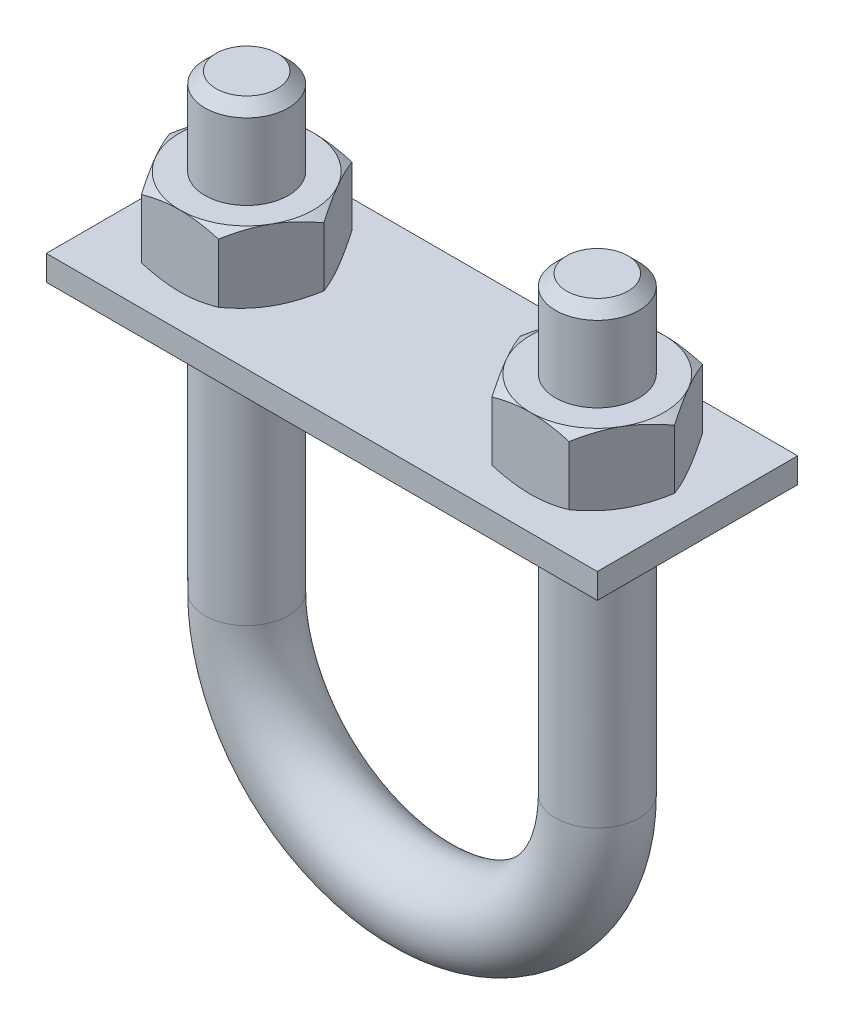
SolidWorks part; units mm, degrees
ref_plane "Front" through (0, 0, 0) normal (0, 0, 1) x (1, 0, 0)
ref_plane "Top" through (0, 0, 0) normal (0, 1, 0) x (1, 0, 0)
ref_plane "Right" through (0, 0, 0) normal (1, 0, 0) x (0, 0, -1)
sketch "Sketch1" plane through (0, 0, 0) normal (0, 0, 1) x (1, 0, 0)
  line L0 (-12.7, 42.8625) -> (-20.6375, 42.8625) construction
  line L1 (-16.6687, 42.8625) -> (-16.6687, 0) construction
  line L3 (16.6687, 0) -> (16.6687, 42.8625) construction
  line L4 (20.6375, 42.8625) -> (12.7, 42.8625) construction
  line L5 (-12.7, 7.9375) -> (-20.6375, 7.9375)
  line L6 (0, -12.7) -> (0, -20.6375) construction
  arc A0 (-16.6687, 0) -> (16.6687, 0) centre (0, 0) ccw construction
  circle A1 centre (0, 0) radius 12.7 construction
  point P5 (0, -16.6687)
  point P8 (-16.6687, 31.2208)
  point P15 (-16.6688, 19.5792)
  dimension "Dia" = 7.9375
  dimension "D5" = 11.6417
  dimension "D6" = 11.6417
ref_plane "Plane3" through (0, 42.8625, 0) normal (0, 1, 0) x (-1, 0, 0)
sketch "Sketch2" plane through (0, 42.8625, 0) normal (0, 1, 0) x (-1, 0, 0)
  circle A0 centre (16.6687, 0) radius 3.9688
extrude "Boss-Extrude1" add sketch "Sketch2" against normal up to vertex (34.925 mm away) up to point (-12.7, 7.9375, 0)
sketch "Sketch6" plane through (0, 42.8625, 0) normal (0, 1, 0) x (1, 0, 0)
  circle A1 centre (-16.6687, 0) radius 3.9688
  circle A2 centre (-16.6687, 0) radius 3.9688
  dimension "D1" = 0
curve "Helix/Spiral1" pitch 1.4111 height 36.3361 turns 25.75 parameters "Pitch"=1.4111
chamfer "Chamfer2" distance 1.0583 angle 45 1 edges at (-16.6687, 42.8625, 3.9688)
sketch "Sketch4" plane through (0, 0, 0) normal (0, 0, 1) x (1, 0, 0)
  line L0 (-12.7, 42.8625) -> (-12.7, 44.0972)
  line L1 (-12.7, 44.0972) -> (-13.6165, 43.5681)
  line L2 (-13.6165, 43.5681) -> (-13.6165, 43.3917)
  line L3 (-13.6165, 43.3917) -> (-12.7, 42.8625)
  line L4 (-13.6165, 43.4799) -> (-12.7, 43.4799) construction
  line L5 (-13.1583, 43.8326) -> (-13.1583, 43.1271) construction
  line L7 (-12.7, 42.8625) -> (-20.6375, 42.8625) construction
  dimension "D1" = 60
  dimension "D2" = 0.7056
  dimension "D3" = 0.1764
sweep "Threads" [suppressed] cut profiles "Sketch4" path "Helix/Spiral1"
ref_plane "Plane5" through (0, 7.9375, 0) normal (0, 1, 0) x (-1, 0, 0)
sketch "Sketch7" plane through (0, 7.9375, 0) normal (0, 1, 0) x (-1, 0, 0)
  line L0 (12.7, 0) -> (20.6375, 0) construction
  circle A0 centre (16.6687, 0) radius 3.9688
  circle A1 centre (16.6687, 0) radius 3.9688 construction
sketch "Sketch8" plane through (0, 0, 0) normal (0, 0, 1) x (1, 0, 0)
  line L0 (-16.6687, 42.8625) -> (-16.6687, 0) construction
  line L1 (16.6687, 0) -> (16.6687, 42.8625) construction
  line L2 (-16.6687, 7.9375) -> (-16.6687, 0)
  line L3 (16.6687, 0) -> (16.6687, 7.9375)
  line L4 (47.1487, 7.9375) -> (-47.1487, 7.9375) construction
  arc A0 (-16.6687, 0) -> (16.6687, 0) centre (0, 0) ccw construction
  arc A1 (-16.6687, 0) -> (16.6687, 0) centre (0, 0) ccw
sweep "Sweep1" add profiles "Sketch7" path "Sketch8"
move or copy body "Body-Move/Copy1" bodies to move or copy 109 copy yes number of copies 1 translate (33.3375, 0, 0) parameters "D1"=0, "D2"=0, "D3"=0
combine bodies "Combine1" operation type add bodies to combine 109 112 111
ref_plane "Plane6" through (0, 31.2208, 0) normal (0, 1, 0) x (-1, 0, 0)
sketch "Sketch9" plane through (0, 31.2208, 0) normal (0, 1, 0) x (-1, 0, 0)
  line L0 (-20.6375, 0) -> (-12.7, 0) construction
  line L1 (-20.3349, 6.35) -> (-24.0011, 0)
  line L2 (-24.0011, 0) -> (-20.3349, -6.35)
  line L3 (-20.3349, -6.35) -> (-13.0026, -6.35)
  line L4 (-13.0026, -6.35) -> (-9.3364, 0)
  line L5 (-9.3364, 0) -> (-13.0026, 6.35)
  line L6 (-13.0026, 6.35) -> (-20.3349, 6.35)
  circle A0 centre (-16.6688, 0) radius 6.35 construction
  circle A1 centre (-16.6688, 0) radius 3.9688
  circle A2 centre (16.6687, 0) radius 3.9688 construction
  dimension "Nut Size" = 12.7
extrude "Boss-Extrude2" add sketch "Sketch9" along normal mid plane 6.7469 separate body
sketch "Sketch10" plane through (0, 34.5943, 0) normal (0, 1, 0) x (1, 0, 0)
  circle A0 centre (16.6688, 0) radius 6.35 construction
  circle A1 centre (16.6688, 0) radius 6.35
extrude "Cut-Extrude1" cut sketch "Sketch10" against normal through all draft 60 flip side to cut
sketch "Sketch11" plane through (0, 27.8474, 0) normal (0, -1, 0) x (1, 0, 0)
  circle A1 centre (16.6688, 0) radius 6.35
  circle A2 centre (16.6688, 0) radius 6.35
  dimension "D1" = 0
extrude "Cut-Extrude2" cut sketch "Sketch11" against normal through all draft 60 flip side to cut
move or copy body "Body-Move/Copy2" bodies to move or copy 116 copy yes number of copies 1 translate (-33.3375, 0, 0) parameters "D1"=0, "D2"=0, "D3"=0
move or copy body "2nd set nuts" [suppressed] bodies to move or copy 117 116 copy yes number of copies 1 translate (0, -11.6417, 0) parameters "D1"=0, "D2"=0, "D3"=0
sketch "Sketch12" plane through (0, 27.8474, 0) normal (0, 1, 0) x (1, 0, 0)
  line L1 (26.1937, -9.525) -> (-26.1937, -9.525)
  line L2 (26.1937, -9.525) -> (26.1937, 9.525)
  line L3 (26.1937, 9.525) -> (-26.1937, 9.525)
  line L4 (-26.1937, -9.525) -> (-26.1937, 9.525)
  line L5 (26.1937, -9.525) -> (-26.1937, 9.525) construction
  line L6 (26.1937, 9.525) -> (-26.1937, -9.525) construction
  point P0 (0, 0)
  dimension "Mounting Plate Lg" = 52.3875
  dimension "Mounting Plate Wd" = 19.05
extrude "Boss-Extrude3" add sketch "Sketch12" against normal blind 2.3813
equation "\"D3@Helix/Spiral1\" = \"Thread Lg@Sketch1\"+\"Pitch@Helix/Spiral1\""
equation "\"D3@Sketch4\" = \"Pitch@Helix/Spiral1\"*.125"
equation "\"D2@Sketch4\" = \"Pitch@Helix/Spiral1\"*.5"
equation "\"D1@Chamfer2\" = \"Pitch@Helix/Spiral1\"*.75"
equation "\"D5@Sketch1\" = \"Thread Lg@Sketch1\"/3"
equation "\"D6@Sketch1\" = \"Thread Lg@Sketch1\"/3"
